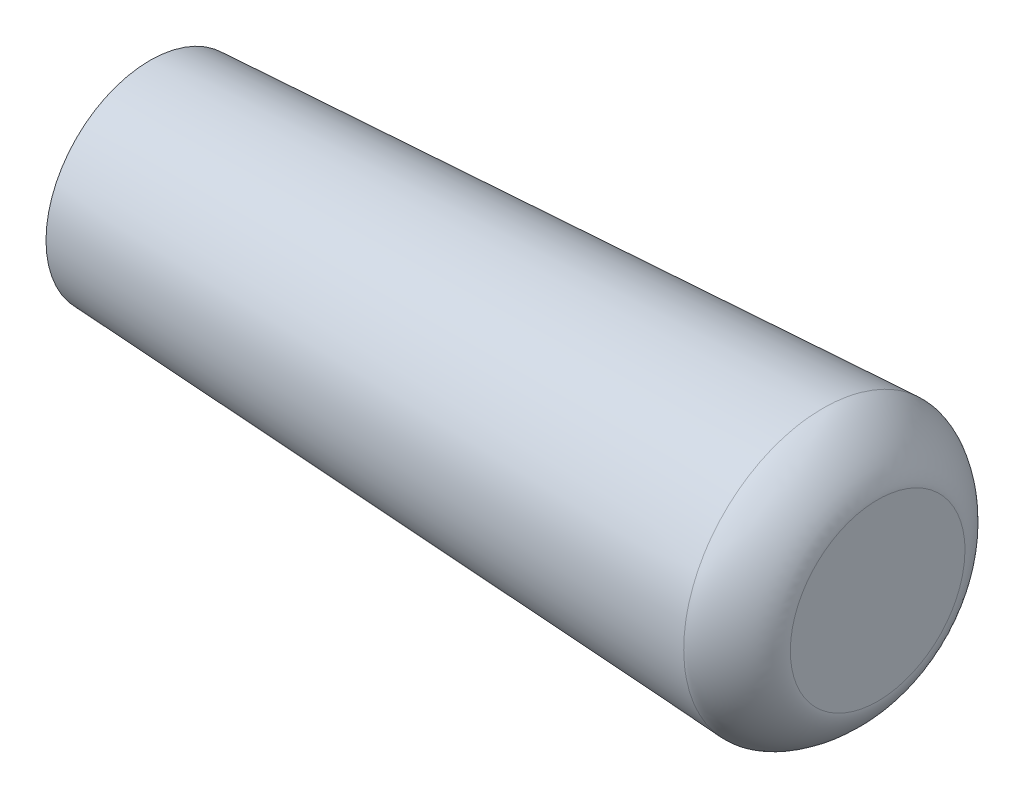
SolidWorks part; units mm, degrees
ref_plane "Płaszczyzna przednia" through (0, 0, 0) normal (0, 0, 1) x (1, 0, 0)
ref_plane "Płaszczyzna górna" through (0, 0, 0) normal (0, 1, 0) x (1, 0, 0)
ref_plane "Płaszczyzna prawa" through (0, 0, 0) normal (1, 0, 0) x (0, 0, -1)
sketch "Szkic1" plane through (0, 0, 0) normal (1, 0, 0) x (0, 0, -1)
  circle A0 centre (0, 0) radius 10
  dimension "D1" = 20
extrude "Dodanie-wyciągnięcie1" add sketch "Szkic1" along normal blind 70 draft 3 draft outward yes
fillet "Zaokrąglenie1" radius 5 1 edges at (70, 0, -13.6685)
sketch "Szkic2" plane through (0, 0, 0) normal (-1, 0, 0) x (0, 0, 1)
  line L1 (-4.765, -7.53) -> (4.765, -7.53)
  line L2 (-4.765, -7.53) -> (-4.765, 7.53)
  line L3 (-4.765, 7.53) -> (4.765, 7.53)
  line L4 (4.765, -7.53) -> (4.765, 7.53)
  line L5 (-4.765, -7.53) -> (4.765, 7.53) construction
  line L6 (-4.765, 7.53) -> (4.765, -7.53) construction
  point P0 (0, 0)
  dimension "D1" = 9.53
  dimension "D2" = 15.06
extrude "Wytnij-wyciągnięcie1" cut sketch "Szkic2" against normal blind 60
